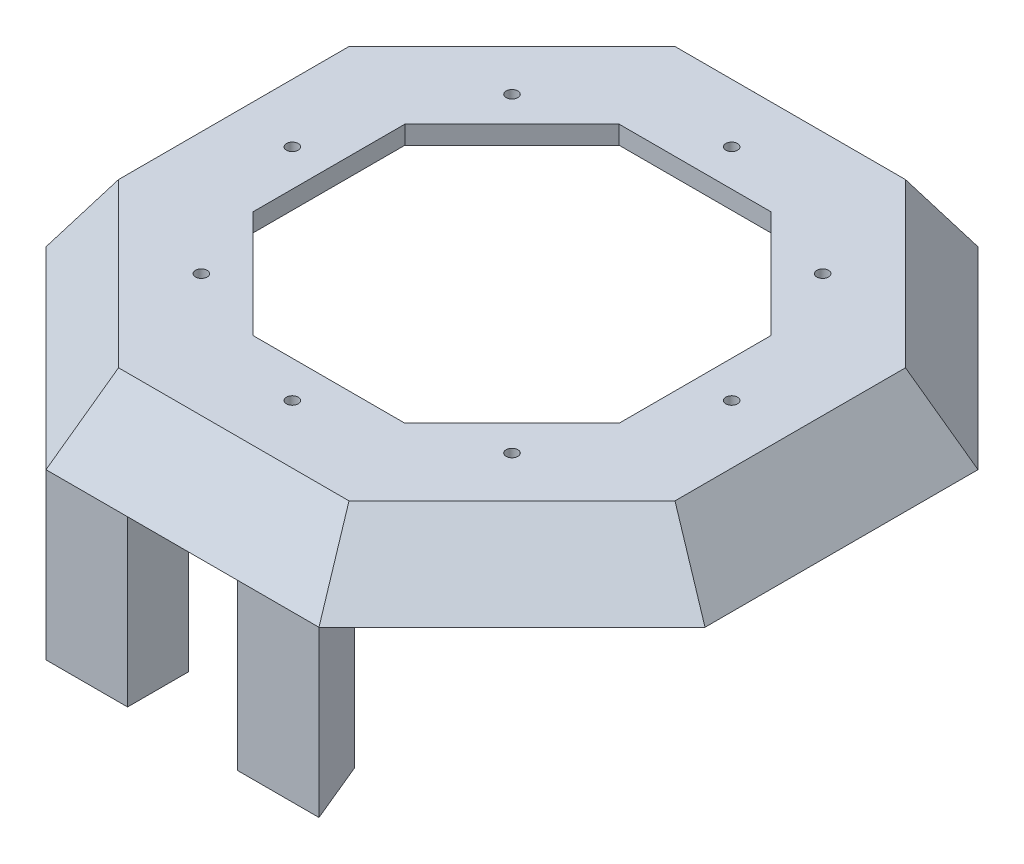
SolidWorks part; units mm, degrees
ref_plane "Front Plane" through (0, 0, 0) normal (0, 0, 1) x (1, 0, 0)
ref_plane "Top Plane" through (0, 0, 0) normal (0, 1, 0) x (1, 0, 0)
ref_plane "Right Plane" through (0, 0, 0) normal (1, 0, 0) x (0, 0, -1)
sketch "Sketch1" plane through (0, 0, 0) normal (0, 1, 0) x (1, 0, 0)
  line L1 (90, -37.2792) -> (90, 37.2792)
  line L2 (90, 37.2792) -> (37.2792, 90)
  line L3 (37.2792, 90) -> (-37.2792, 90)
  line L4 (-37.2792, 90) -> (-90, 37.2792)
  line L5 (-90, 37.2792) -> (-90, -37.2792)
  line L6 (-90, -37.2792) -> (-37.2792, -90)
  line L7 (-37.2792, -90) -> (37.2792, -90)
  line L8 (37.2792, -90) -> (90, -37.2792)
  circle A0 centre (0, 0) radius 90 construction
  dimension "D1" = 180
extrude "Initial extrude" add sketch "Sketch1" along normal blind 20
chamfer "Top chamfer" distance 20 angle 35 8 edges at (0, 20, 90) (-63.6396, 20, 63.6396) (-90, 20, 0) (-63.6396, 20, -63.6396) (0, 20, -90) (63.6396, 20, -63.6396) (90, 20, 0) (63.6396, 20, 63.6396) first distance on face at (0, 10, 90) first distance on face at (-63.6396, 10, 63.6396) first distance on face at (-90, 10, 0) first distance on face at (-63.6396, 10, -63.6396) first distance on face at (0, 10, -90) first distance on face at (63.6396, 10, -63.6396) first distance on face at (90, 10, 0) first distance on face at (63.6396, 10, 63.6396)
shell "Top shell" thickness 5 removed face at (0, 0, 0)
sketch "Sketch2" plane through (0, 20, 0) normal (0, 1, 0) x (1, 0, 0)
  line L1 (20.7107, 50) -> (-20.7107, 50)
  line L2 (-20.7107, 50) -> (-50, 20.7107)
  line L3 (-50, 20.7107) -> (-50, -20.7107)
  line L4 (-50, -20.7107) -> (-20.7107, -50)
  line L5 (-20.7107, -50) -> (20.7107, -50)
  line L6 (20.7107, -50) -> (50, -20.7107)
  line L7 (50, -20.7107) -> (50, 20.7107)
  line L8 (50, 20.7107) -> (20.7107, 50)
  circle A0 centre (0, 0) radius 50 construction
  dimension "D1" = 100
extrude "Interior hex hole" cut sketch "Sketch2" against normal through all
sketch "Sketch3" plane through (0, 15, 0) normal (0, -1, 0) x (1, 0, 0)
  line L0 (-50, -20.7107) -> (-50, 20.7107) construction
  circle A0 centre (-60, 0) radius 1.6
  circle A1 centre (-42.4264, 42.4264) radius 1.6
  circle A2 centre (0, 60) radius 1.6
  circle A3 centre (42.4264, 42.4264) radius 1.6
  circle A4 centre (60, 0) radius 1.6
  circle A5 centre (42.4264, -42.4264) radius 1.6
  circle A6 centre (0, -60) radius 1.6
  circle A7 centre (-42.4264, -42.4264) radius 1.6
  point P22 (0, 0)
  dimension "D1" = 3.2
  dimension "D2" = 10
  dimension "D3" = 8
extrude "Top screw holes" cut sketch "Sketch3" against normal through all
sketch "Sketch5" plane through (0, 0, 0) normal (0, -1, 0) x (1, 0, 0)
  line L0 (-34.7509, 83.8961) -> (-30.4004, 73.393)
  line L1 (-30.4004, 73.393) -> (-15, 73.393)
  line L2 (30.4004, 73.393) -> (37.2792, 90)
  line L3 (37.2792, 90) -> (15, 90)
  line L4 (-37.2792, 90) -> (-34.7509, 83.8961)
  line L5 (-15, 90) -> (-15, 73.393)
  line L6 (15, 90) -> (15, 73.393)
  line L7 (-15, 90) -> (-37.2792, 90)
  line L8 (15, 73.393) -> (30.4004, 73.393)
  line L9 (-37.2792, 90) -> (37.2792, 90) construction
  circle A0 centre (-22, 80.5) radius 1.6
  circle A1 centre (22, 80.5) radius 1.6
  point P15 (0, 90)
  line M8 (-34.7509, 83.8961) -> (34.7509, 83.8961)
  line M17 (37.2792, 90) -> (-37.2792, 90)
  dimension "D1" = 3.2
  dimension "D2" = 9.5
  dimension "D3" = 15
  dimension "D4" = 15
  dimension "D5" = 7
  dimension "D6" = 7
extrude "Boss-Extrude2" add sketch "Sketch5" along normal blind 45 contours A0 | L6 L2 M17 M8 | L6 L8 L2 A1 M8 | L7 L4 L0 L1 L5 region at (23.9162, 0, 78.7866) region at (25.5202, 0, 87.0093) region at (-22, 0, 80.5)
